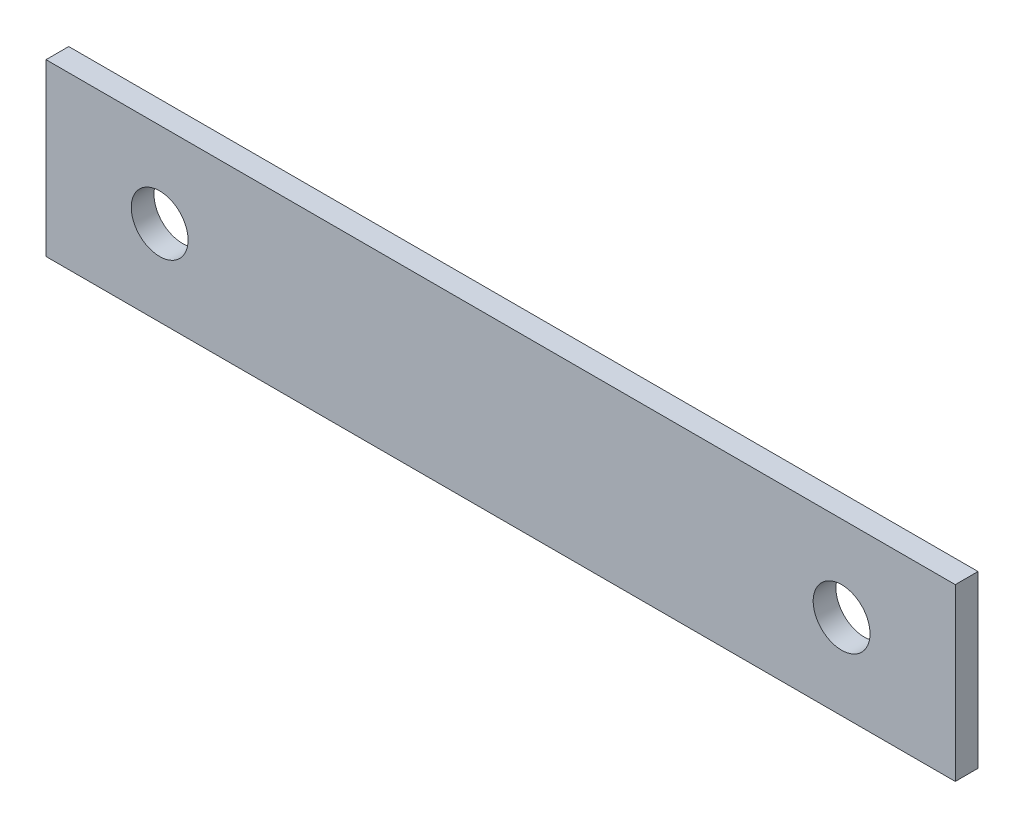
SolidWorks part; units mm, degrees
ref_plane "Front Plane" through (0, 0, 0) normal (0, 0, 1) x (1, 0, 0)
ref_plane "Top Plane" through (0, 0, 0) normal (0, 1, 0) x (1, 0, 0)
ref_plane "Right Plane" through (0, 0, 0) normal (1, 0, 0) x (0, 0, -1)
sketch "Sketch1" plane through (0, 0, 0) normal (0, 0, 1) x (1, 0, 0)
  line L1 (0, 0) -> (80, 0)
  line L2 (0, 0) -> (0, 15)
  line L3 (0, 15) -> (80, 15)
  line L4 (80, 0) -> (80, 15)
  dimension "D1" = 15
  dimension "D2" = 80
base flange "Base-Flange1" sketch "Sketch1" thickness 2 reverse thickness direction no parameters "D1"=0.7366
sketch "Sketch6" plane through (0, 0, 0) normal (0, 0, 1) x (1, 0, 0)
  line L0 (0, 15) -> (0, 0) construction
  line L2 (80, 15) -> (0, 15) construction
  circle A0 centre (10, 7.5) radius 2.5
  circle A1 centre (70, 7.5) radius 2.5
  dimension "D1" = 5
  dimension "D3" = 10
  dimension "D2" = 60
  dimension "D4" = 7.5
extrude "Cut-Extrude1" cut sketch "Sketch6" against normal up to next normal cut yes
sketch "Bend-Lines1" plane through (0, 0, 0) normal (0, 1, 0) x (1, 0, 0)
sketch "Bounding-Box1" plane through (0, 0, 0) normal (0, 1, 0) x (1, 0, 0)
sheet metal parameters "Sheet-Metal1" thickness 2 parameters "D1"=0.7366
flat pattern "Flat-Pattern1" [suppressed]
sketch "Bend-Lines2" plane through (0, 0, 0) normal (0, 1, 0) x (1, 0, 0)
sketch "Bounding-Box2" [suppressed] plane through (0, 0, 0) normal (0, 1, 0) x (1, 0, 0)
sheet metal parameters "Sheet-Metal2" thickness 2 parameters "D1"=0.7366
flat pattern "Flat-Pattern1"
sketch "Bend-Lines2" plane through (0, 0, 0) normal (0, 1, 0) x (1, 0, 0)
sketch "Bounding-Box2" [suppressed] plane through (0, 0, 0) normal (0, 1, 0) x (1, 0, 0)
